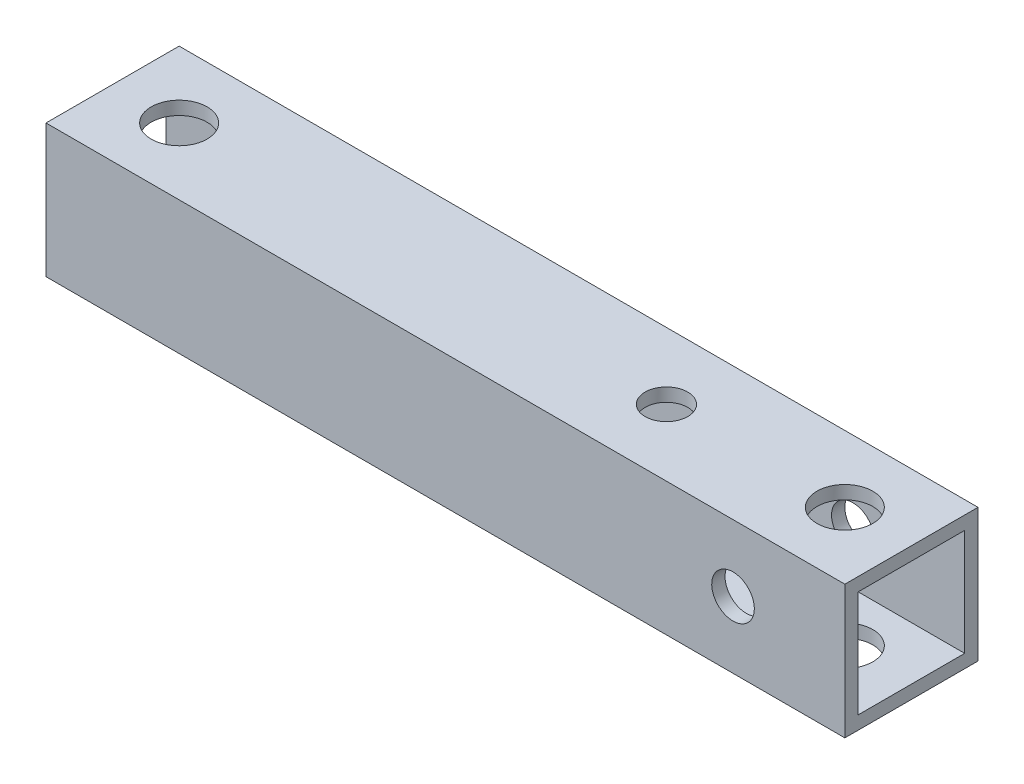
SolidWorks part; units mm, degrees
material "5052-H34"
ref_plane "正面" through (0, 0, 0) normal (0, 0, 1) x (1, 0, 0)
ref_plane "平面" through (0, 0, 0) normal (0, 1, 0) x (1, 0, 0)
ref_plane "右側面" through (0, 0, 0) normal (1, 0, 0) x (0, 0, -1)
sketch "ｽｹｯﾁ1" plane through (0, 0, 0) normal (1, 0, 0) x (0, 0, -1)
  line L1 (-5, 5) -> (5, 5)
  line L2 (-5, 5) -> (-5, -5)
  line L3 (-5, -5) -> (5, -5)
  line L4 (5, 5) -> (5, -5)
  line L5 (-5, 5) -> (5, -5) construction
  line L6 (-5, -5) -> (5, 5) construction
  point P0 (0, 0)
  dimension "D1" = 10
  dimension "D2" = 10
extrude "押し出し-薄板1" add sketch "ｽｹｯﾁ1" along normal blind 60 thin thin type one direction reverse wall 1
sketch "ｽｹｯﾁ2" plane through (0, 5, 0) normal (0, 1, 0) x (1, 0, 0)
  line L0 (30, 5) -> (30, -5) construction
  line L1 (60, 5) -> (0, 5) construction
  line L2 (60, -5) -> (0, -5) construction
  line L3 (30, 0) -> (55, 0) construction
  line L4 (30, 0) -> (0, 0) construction
  line L5 (60, 5) -> (60, -5) construction
  line L6 (0, 5) -> (0, -5) construction
  circle A0 centre (55, 0) radius 2.1
  circle A1 centre (5, 0) radius 2.1
  circle A3 centre (41.6, 0) radius 1.6
  point P15 (0, 0)
  dimension "D1" = 4.2
  dimension "D4" = 3.2
  dimension "D3" = 11.6
  dimension "D2" = 5
extrude "ｶｯﾄ - 押し出し1" cut sketch "ｽｹｯﾁ2" against normal through all
sketch "ｽｹｯﾁ3" plane through (0, 0, -5) normal (0, 0, -1) x (-1, 0, 0)
  line L0 (-30, 5) -> (-30, -5) construction
  line L1 (-60, 5) -> (0, 5) construction
  line L2 (-60, -5) -> (0, -5) construction
  line L3 (-30, 0) -> (-51.6, 0) construction
  circle A0 centre (-51.6, 0) radius 1.6
  dimension "D2" = 3.2
  dimension "D1" = 21.6
extrude "ｶｯﾄ - 押し出し2" cut sketch "ｽｹｯﾁ3" against normal through all
